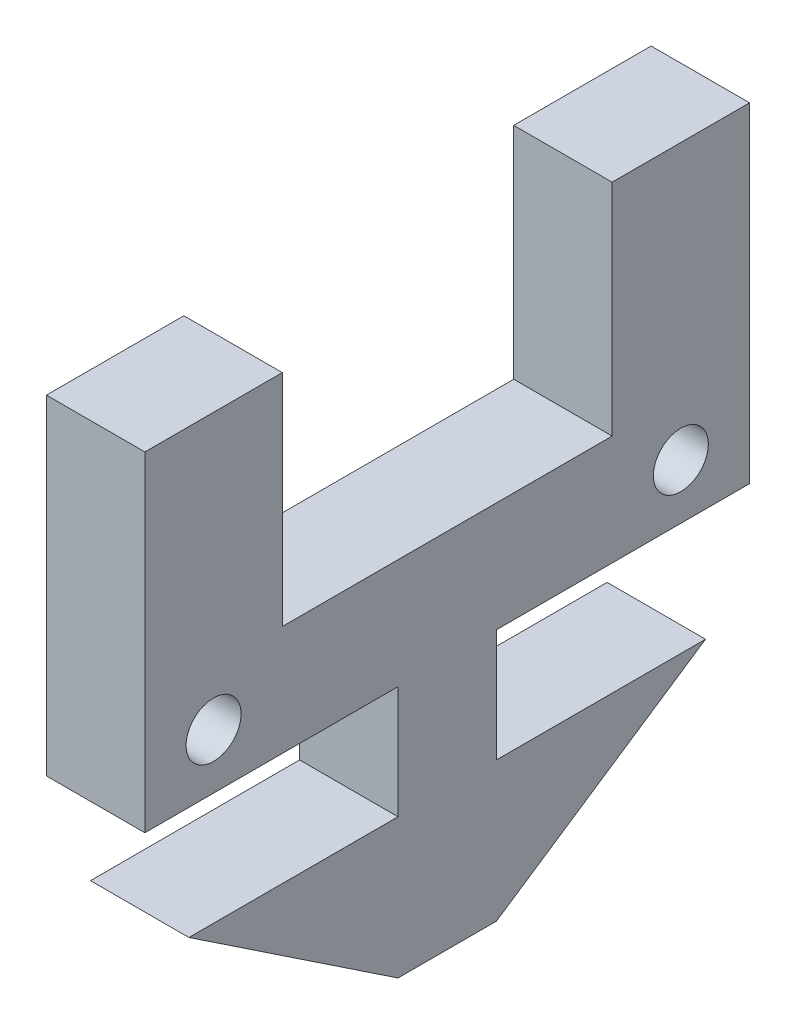
SolidWorks part; units mm, degrees
other "DetailItem2"
ref_plane "Front Plane" through (0, 0, 0) normal (0, 0, 1) x (1, 0, 0)
ref_plane "Top Plane" through (0, 0, 0) normal (0, 1, 0) x (1, 0, 0)
ref_plane "Right Plane" through (0, 0, 0) normal (1, 0, 0) x (0, 0, -1)
sketch "Sketch1" plane through (0, 0, 0) normal (1, 0, 0) x (0, 0, -1)
  line L0 (-6, 6) -> (-6, -2)
  line L1 (-11, -6) -> (11, -6)
  line L2 (-11, -6) -> (-11, 6)
  line L3 (-11, 6) -> (-6, 6)
  line L4 (11, -6) -> (11, 6)
  line L5 (-11, -6) -> (11, 6) construction
  line L6 (-11, 6) -> (11, -6) construction
  line L7 (-6, -2) -> (6, -2)
  line L8 (6, -2) -> (6, 6)
  line L9 (6, 6) -> (11, 6)
  point P0 (0, 0)
  point P8 (0, -2)
  dimension "D1" = 12
  dimension "D2" = 22
  dimension "D3" = 5
  dimension "D4" = 4
extrude "Boss-Extrude1" add sketch "Sketch1" along normal blind 3.5814
sketch "Sketch7" plane through (3.5814, 0, 0) normal (1, 0, 0) x (0, 0, -1)
  line L2 (-6, 6) -> (-11, 6) construction
  line L3 (-8.5, -4) -> (8.5, -4) construction
  circle A0 centre (-8.5, -4) radius 1
  circle A1 centre (8.5, -4) radius 1
  point P4 (0, -4)
  dimension "D1" = 2
  dimension "D2" = 17
  dimension "D3" = 10
extrude "Cut-Extrude5" cut sketch "Sketch7" against normal through all
sketch "Sketch8" plane through (0, 0, 0) normal (1, 0, 0) x (0, 0, -1)
  line L9 (-1.7907, -10.1) -> (-9.398, -10.1)
  line L10 (-1.7907, -6) -> (-1.7907, -10.1)
  line L11 (1.7907, -6) -> (1.7907, -10.1)
  line L12 (-9.398, -10.1) -> (-1.7907, -15.18)
  line L13 (-1.7907, -15.18) -> (1.7907, -15.18)
  line L14 (1.7907, -15.18) -> (9.398, -10.1)
  line L15 (9.398, -10.1) -> (1.7907, -10.1)
  line L16 (-11, -6) -> (11, -6) construction
  line L17 (-1.7907, -6) -> (1.7907, -6)
  point P0 (0, -8.05)
  point P9 (0, -15.18)
  point P10 (1.7907, -8.05)
  dimension "D1" = 3.5814
  dimension "D2" = 4.1
  dimension "D3" = 18.796
  dimension "D4" = 5.08
extrude "Boss-Extrude3" add sketch "Sketch8" along normal up to surface (3.5814 mm away) up to face at (3.5814, -4, 7.5)
